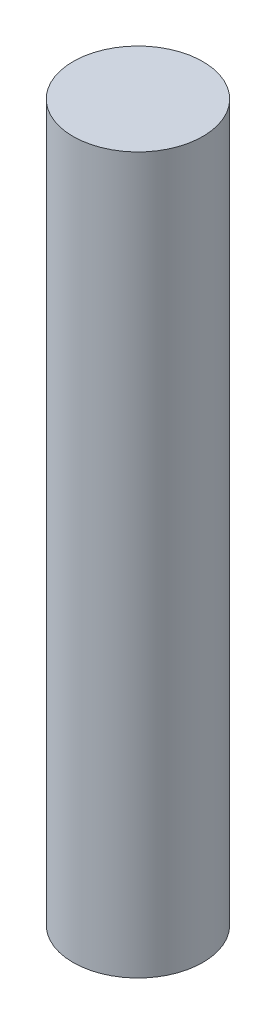
SolidWorks part; units mm, degrees
material "Plain Carbon Steel"
ref_plane "Front Plane" through (0, 0, 0) normal (0, 0, 1) x (1, 0, 0)
ref_plane "Top Plane" through (0, 0, 0) normal (0, 1, 0) x (1, 0, 0)
ref_plane "Right Plane" through (0, 0, 0) normal (1, 0, 0) x (0, 0, -1)
sketch "Sketch1" plane through (0, 0, 0) normal (0, 1, 0) x (1, 0, 0)
  circle A0 centre (0, 0) radius 6.35
  dimension "D1" = 12.7
extrude "Boss-Extrude1" add sketch "Sketch1" along normal blind 70
